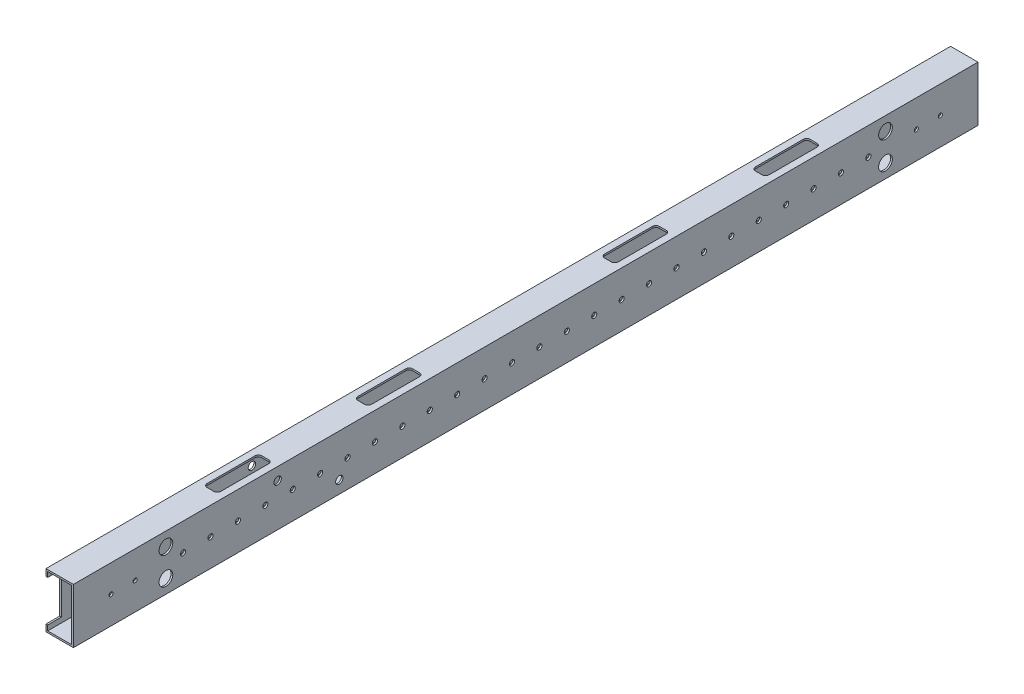
SolidWorks part; units mm, degrees
ref_plane "Front Plane" through (0, 0, 0) normal (0, 0, 1) x (1, 0, 0)
ref_plane "Top Plane" through (0, 0, 0) normal (0, 1, 0) x (1, 0, 0)
ref_plane "Right Plane" through (0, 0, 0) normal (1, 0, 0) x (0, 0, -1)
sketch "Sketch1" plane through (0, 0, 0) normal (0, 0, 1) x (1, 0, 0)
  line L1 (-12.7, -25.4) -> (12.7, -25.4)
  line L2 (-12.7, -25.4) -> (-12.7, 25.4)
  line L3 (-12.7, 25.4) -> (12.7, 25.4)
  line L4 (12.7, -25.4) -> (12.7, 25.4)
  line L5 (-12.7, -25.4) -> (12.7, 25.4) construction
  line L6 (-12.7, 25.4) -> (12.7, -25.4) construction
  line L7 (-11.1125, -23.8125) -> (11.1125, -23.8125)
  line L8 (-11.1125, -23.8125) -> (-11.1125, 23.8125)
  line L9 (-11.1125, 23.8125) -> (11.1125, 23.8125)
  line L10 (11.1125, -23.8125) -> (11.1125, 23.8125)
  line L11 (-11.1125, -23.8125) -> (11.1125, 23.8125) construction
  line L12 (-11.1125, 23.8125) -> (11.1125, -23.8125) construction
  point P0 (0, 0)
  point P1 (0, 0)
  point P7 (0, 0)
  dimension "D1" = 25.4
  dimension "D2" = 50.8
  dimension "D3" = 1.5875
  dimension "D4" = 1.5875
extrude "Boss-Extrude1" add sketch "Sketch1" along normal blind 838.2
sketch "Sketch2" plane through (12.7, 0, 0) normal (1, 0, 0) x (0, 0, -1)
  line L0 (-85.725, 25.4) -> (-85.725, -25.4) construction
  line L1 (-73.025, 25.4) -> (-98.425, 25.4) construction
  line L2 (-73.025, 25.4) -> (-73.025, -25.4) construction
  line L3 (-73.025, -25.4) -> (-98.425, -25.4) construction
  line L4 (-98.425, 25.4) -> (-98.425, -25.4) construction
  line L5 (0, 25.4) -> (0, -25.4) construction
  line L6 (-838.2, 25.4) -> (0, 25.4) construction
  line L7 (-838.2, -25.4) -> (0, -25.4) construction
  line L8 (0, -25.4) -> (0, 25.4) construction
  line L9 (-765.175, 25.4) -> (-739.775, 25.4) construction
  line L10 (-765.175, 25.4) -> (-765.175, -25.4) construction
  line L11 (-765.175, -25.4) -> (-739.775, -25.4) construction
  line L12 (-739.775, 25.4) -> (-739.775, -25.4) construction
  line L13 (-838.2, -25.4) -> (-838.2, 25.4) construction
  line L14 (-752.475, 25.4) -> (-752.475, -25.4) construction
  line L15 (-419.1, 25.4) -> (-419.1, -25.4) construction
  line L16 (-838.2, 25.4) -> (0, 25.4) construction
  line L17 (-838.2, -25.4) -> (0, -25.4) construction
  circle A0 centre (-85.725, 12.7) radius 3.175
  circle A1 centre (-85.725, -12.7) radius 3.175
  circle A2 centre (-752.475, 12.7) radius 3.175
  circle A3 centre (-752.475, -12.7) radius 3.175
  circle A4 centre (-57.15, 0) radius 1.905
  circle A5 centre (-34.798, 0) radius 1.905
  circle A6 centre (-803.402, 0) radius 1.905
  circle A7 centre (-781.05, 0) radius 1.905
  dimension "D6" = 6.35
  dimension "D9" = 3.81
  dimension "D2" = 25.4
  dimension "D3" = 50.8
  dimension "D4" = 25.4
  dimension "D1" = 73.025
  dimension "D5" = 73.025
  dimension "D7" = 12.7
  dimension "D8" = 25.4
  dimension "D10" = 57.15
  dimension "D11" = 2
extrude "Cut-Extrude1" cut sketch "Sketch2" against normal through all
sketch "Sketch3" plane through (12.7, 0, 0) normal (1, 0, 0) x (0, 0, -1)
  circle A0 centre (-752.475, 12.7) radius 6.35
  circle A1 centre (-752.475, -12.7) radius 6.35
  circle A2 centre (-85.725, 12.7) radius 6.35
  circle A3 centre (-85.725, -12.7) radius 6.35
  dimension "D1" = 12.7
extrude "Cut-Extrude2" cut sketch "Sketch3" against normal up to next
sketch "Sketch4" plane through (-12.7, 0, 0) normal (-1, 0, 0) x (0, 0, 1)
  line L0 (0, 25.4) -> (0, -25.4) construction
  line L1 (0, 19.05) -> (12.7, 19.05)
  line L2 (0, 19.05) -> (0, -19.05)
  line L3 (0, -19.05) -> (12.7, -19.05)
  line L4 (12.7, 19.05) -> (12.7, -19.05)
  line L5 (838.2, 25.4) -> (0, 25.4) construction
  line L6 (419.1, 25.4) -> (419.1, -25.4) construction
  line L7 (838.2, -25.4) -> (0, -25.4) construction
  line L8 (825.5, 19.05) -> (825.5, -19.05)
  line L9 (838.2, -19.05) -> (825.5, -19.05)
  line L10 (838.2, 19.05) -> (838.2, -19.05)
  line L11 (838.2, 19.05) -> (825.5, 19.05)
  dimension "D1" = 38.1
  dimension "D2" = 12.7
  dimension "D3" = 6.35
extrude "Cut-Extrude3" cut sketch "Sketch4" against normal blind 3.175
sketch "Sketch5" plane through (12.7, 0, 0) normal (1, 0, 0) x (0, 0, -1)
  line L0 (-838.2, -25.4) -> (-838.2, 25.4) construction
  line L1 (-838.2, 25.4) -> (0, 25.4) construction
  circle A0 centre (-736.6, 0) radius 2.3812
  circle A2 centre (-711.2, 0) radius 2.3812
  circle A3 centre (-685.8, 0) radius 2.3812
  circle A4 centre (-660.4, 0) radius 2.3812
  circle A5 centre (-635, 0) radius 2.3812
  circle A6 centre (-609.6, 0) radius 2.3812
  circle A7 centre (-584.2, 0) radius 2.3812
  circle A8 centre (-558.8, 0) radius 2.3812
  circle A9 centre (-533.4, 0) radius 2.3812
  circle A10 centre (-508, 0) radius 2.3812
  circle A11 centre (-482.6, 0) radius 2.3812
  circle A12 centre (-457.2, 0) radius 2.3812
  circle A13 centre (-431.8, 0) radius 2.3812
  circle A14 centre (-406.4, 0) radius 2.3812
  circle A15 centre (-381, 0) radius 2.3812
  circle A16 centre (-355.6, 0) radius 2.3812
  circle A17 centre (-330.2, 0) radius 2.3812
  circle A18 centre (-304.8, 0) radius 2.3812
  circle A19 centre (-279.4, 0) radius 2.3812
  circle A20 centre (-254, 0) radius 2.3812
  circle A21 centre (-228.6, 0) radius 2.3812
  circle A22 centre (-203.2, 0) radius 2.3812
  circle A23 centre (-177.8, 0) radius 2.3812
  circle A24 centre (-152.4, 0) radius 2.3812
  circle A25 centre (-127, 0) radius 2.3812
  circle A26 centre (-101.6, 0) radius 2.3812
  dimension "D1" = 101.6
  dimension "D2" = 4.7625
  dimension "D3" = 25.4
  dimension "D4" = 26
extrude "Cut-Extrude4" cut sketch "Sketch5" against normal through all
sketch "Sketch6" plane through (0, 25.4, 0) normal (0, 1, 0) x (1, 0, 0)
  line L0 (12.7, 0) -> (-12.7, 0) construction
  line L1 (-3.175, -279.4) -> (3.175, -279.4)
  line L2 (-6.35, -282.575) -> (-6.35, -327.025)
  line L3 (-3.175, -330.2) -> (3.175, -330.2)
  line L4 (6.35, -282.575) -> (6.35, -327.025)
  line L5 (-12.7, -838.2) -> (-12.7, 0) construction
  line L6 (-12.7, -419.1) -> (12.7, -419.1) construction
  line L7 (12.7, -838.2) -> (12.7, 0) construction
  line L8 (6.35, -555.625) -> (6.35, -511.175)
  line L9 (-3.175, -508) -> (3.175, -508)
  line L10 (-6.35, -555.625) -> (-6.35, -511.175)
  line L11 (-3.175, -558.8) -> (3.175, -558.8)
  line L12 (6.35, -695.325) -> (6.35, -650.875)
  line L13 (-3.175, -139.7) -> (3.175, -139.7)
  line L14 (-6.35, -142.875) -> (-6.35, -187.325)
  line L15 (-3.175, -190.5) -> (3.175, -190.5)
  line L16 (6.35, -142.875) -> (6.35, -187.325)
  line L17 (-3.175, -647.7) -> (3.175, -647.7)
  line L18 (-6.35, -695.325) -> (-6.35, -650.875)
  line L19 (-3.175, -698.5) -> (3.175, -698.5)
  arc A0 (3.175, -330.2) -> (6.35, -327.025) centre (3.175, -327.025) ccw
  arc A1 (6.35, -282.575) -> (3.175, -279.4) centre (3.175, -282.575) ccw
  arc A2 (-3.175, -279.4) -> (-6.35, -282.575) centre (-3.175, -282.575) ccw
  arc A3 (-6.35, -327.025) -> (-3.175, -330.2) centre (-3.175, -327.025) ccw
  arc A4 (-6.35, -511.175) -> (-3.175, -508) centre (-3.175, -511.175) cw
  arc A5 (3.175, -508) -> (6.35, -511.175) centre (3.175, -511.175) cw
  arc A6 (6.35, -555.625) -> (3.175, -558.8) centre (3.175, -555.625) cw
  arc A7 (-6.35, -555.625) -> (-3.175, -558.8) centre (-3.175, -555.625) ccw
  arc A8 (-6.35, -187.325) -> (-3.175, -190.5) centre (-3.175, -187.325) ccw
  arc A9 (3.175, -190.5) -> (6.35, -187.325) centre (3.175, -187.325) ccw
  arc A10 (6.35, -142.875) -> (3.175, -139.7) centre (3.175, -142.875) ccw
  arc A11 (-3.175, -139.7) -> (-6.35, -142.875) centre (-3.175, -142.875) ccw
  arc A12 (-3.175, -698.5) -> (-6.35, -695.325) centre (-3.175, -695.325) cw
  arc A13 (6.35, -695.325) -> (3.175, -698.5) centre (3.175, -695.325) cw
  arc A14 (3.175, -647.7) -> (6.35, -650.875) centre (3.175, -650.875) cw
  arc A15 (-6.35, -650.875) -> (-3.175, -647.7) centre (-3.175, -650.875) cw
  point P18 (6.35, -330.2)
  point P21 (6.35, -279.4)
  point P24 (-6.35, -279.4)
  point P27 (-6.35, -330.2)
  point P30 (-6.35, -508)
  point P33 (6.35, -508)
  point P36 (6.35, -558.8)
  point P39 (-6.35, -558.8)
  dimension "D5" = 3.175
  dimension "D6" = 3.175
  dimension "D10" = 3.175
  dimension "D1" = 50.8
  dimension "D2" = 12.7
  dimension "D3" = 279.4
  dimension "D4" = 6.35
  dimension "D7" = 50.8
  dimension "D8" = 6.35
  dimension "D9" = 139.7
extrude "Cut-Extrude5" cut sketch "Sketch6" against normal blind 279.4
ref_plane "Plane1" through (12.7, -25.4, 838.2) normal (0, 0, -1) x (-1, 0, 0)
sketch "Sketch9" plane through (0, -25.4, 0) normal (0, -1, 0) x (1, 0, 0)
  line L0 (-12.7, 419.1) -> (12.7, 419.1) construction
  line L1 (-12.7, 838.2) -> (-12.7, 0) construction
  line L2 (12.7, 838.2) -> (12.7, 0) construction
  line L3 (-12.7, 838.2) -> (12.7, 838.2) construction
  line L4 (3.175, 533.4) -> (-3.175, 533.4)
  line L5 (6.35, 530.225) -> (6.35, 485.775)
  line L6 (3.175, 482.6) -> (-3.175, 482.6)
  line L7 (-6.35, 530.225) -> (-6.35, 485.775)
  line L8 (-6.35, 307.975) -> (-6.35, 352.425)
  line L9 (3.175, 355.6) -> (-3.175, 355.6)
  line L10 (6.35, 307.975) -> (6.35, 352.425)
  line L11 (3.175, 304.8) -> (-3.175, 304.8)
  arc A0 (-6.35, 530.225) -> (-3.175, 533.4) centre (-3.175, 530.225) cw
  arc A1 (3.175, 533.4) -> (6.35, 530.225) centre (3.175, 530.225) cw
  arc A2 (6.35, 485.775) -> (3.175, 482.6) centre (3.175, 485.775) cw
  arc A3 (-3.175, 482.6) -> (-6.35, 485.775) centre (-3.175, 485.775) cw
  arc A4 (-3.175, 355.6) -> (-6.35, 352.425) centre (-3.175, 352.425) ccw
  arc A5 (6.35, 352.425) -> (3.175, 355.6) centre (3.175, 352.425) ccw
  arc A6 (3.175, 304.8) -> (6.35, 307.975) centre (3.175, 307.975) ccw
  arc A7 (-6.35, 307.975) -> (-3.175, 304.8) centre (-3.175, 307.975) ccw
  point P14 (-6.35, 533.4)
  point P21 (-6.35, 482.6)
  point P34 (-6.35, 355.6)
  point P35 (-6.35, 304.8)
  dimension "D3" = 3.175
  dimension "D1" = 50.8
  dimension "D2" = 304.8
  dimension "D4" = 6.35
  dimension "D5" = 12.7
extrude "Cut-Extrude6" cut sketch "Sketch9" against normal blind 3.175
sketch "Sketch10" plane through (-12.7, 0, 0) normal (-1, 0, 0) x (0, 0, 1)
  circle A0 centre (648.97, 13.97) radius 3.429
  circle A1 centre (591.82, -13.97) radius 3.429
extrude "Cut-Extrude7" cut sketch "Sketch10" against normal through all
equation "\"D1@Sketch2\"=\"D5@Sketch2\""
